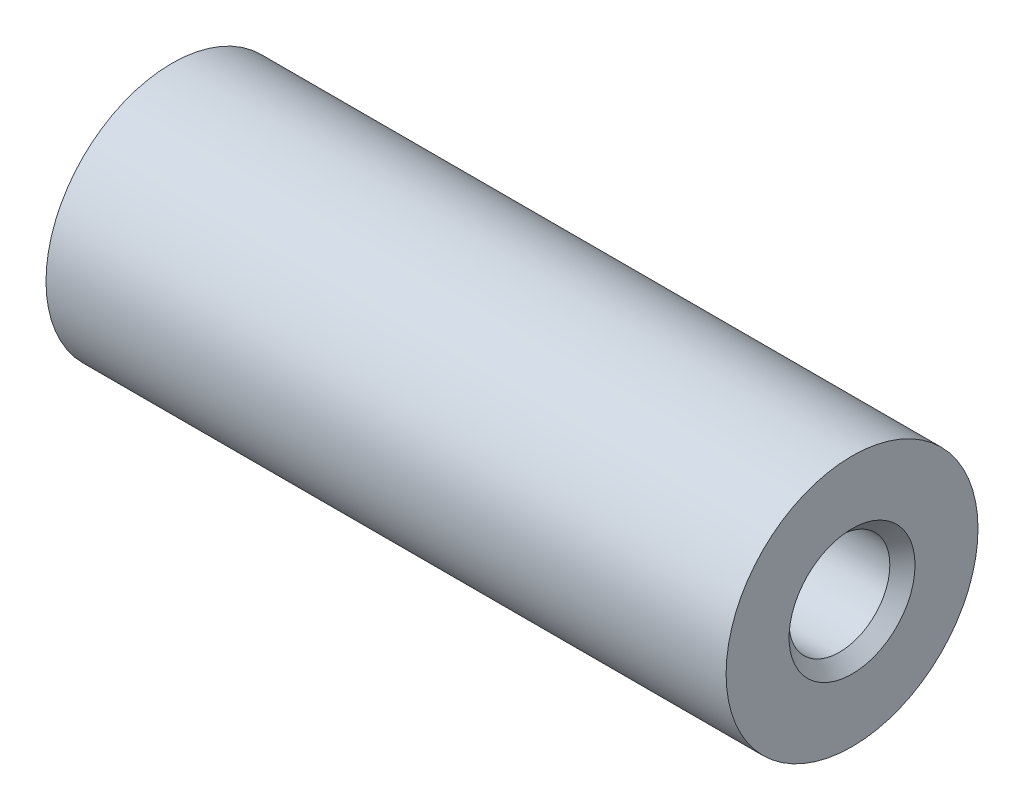
SolidWorks part; units mm, degrees
ref_plane "Ebene vorne" through (0, 0, 0) normal (0, 0, 1) x (1, 0, 0)
ref_plane "Ebene oben" through (0, 0, 0) normal (0, 1, 0) x (1, 0, 0)
ref_plane "Ebene rechts" through (0, 0, 0) normal (1, 0, 0) x (0, 0, -1)
sketch "Skizze1" plane through (0, 0, 0) normal (1, 0, 0) x (0, 0, -1)
  circle A0 centre (0, 0) radius 4
  dimension "D1" = 8
extrude "Aufsatz-Linear austragen1" add sketch "Skizze1" along normal blind 21.6
hole_wizard "Ø3.2 (3.2) Durchmesser Bohrung1" positions "Skizze2" profile "Skizze3" hole size "Ø3.2" standard "ISO" end condition through all
sketch "Skizze2" plane through (21.6, 0, 0) normal (1, 0, 0) x (0, 0, -1)
  point P0 (0, 0)
sketch "Skizze3" plane through (21.6, 0, 0) normal (0, 1, 0) x (0, 0, -1)
  line L0 (0, 0) -> (0, 21.6)
  line L1 (0, 21.6) -> (1.6, 21.6)
  line L2 (1.6, 21.6) -> (1.6, 0)
  line L5 (1.6, 0) -> (0, 0)
  line L11 (0, -6.35) -> (0, 107.95) construction
  dimension "Bohrerdurchmesser" = 3.2
  dimension "Bohrungstiefe" = 21.6
chamfer "Fase1" distance 0.4 angle 45 2 edges at (21.6, 0, -1.6) (0, 0, -1.6)
